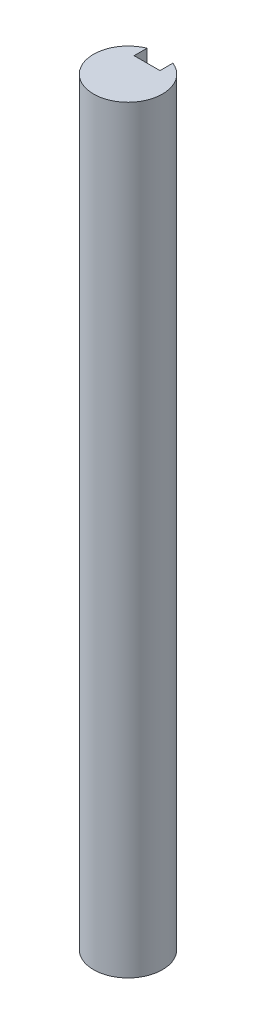
SolidWorks part; units mm, degrees
material "1023 Carbon Steel Sheet (SS)"
ref_plane "Front Plane" through (0, 0, 0) normal (0, 0, 1) x (1, 0, 0)
ref_plane "Top Plane" through (0, 0, 0) normal (0, 1, 0) x (1, 0, 0)
ref_plane "Right Plane" through (0, 0, 0) normal (1, 0, 0) x (0, 0, -1)
sketch "Sketch1" plane through (0, 0, 0) normal (0, 1, 0) x (1, 0, 0)
  line L0 (-1.1906, 2.9433) -> (-1.1906, 1.7527)
  line L1 (-1.1906, 1.7527) -> (1.1906, 1.7527)
  line L2 (1.1906, 1.7527) -> (1.1906, 2.9433)
  arc A0 (-1.1906, 2.9433) -> (1.1906, 2.9433) centre (0, 0) ccw
  point P5 (0, 1.7527)
  dimension "D1" = 6.35
  dimension "D2" = 2.3813
  dimension "D3" = 1.1906
extrude "Boss-Extrude1" add sketch "Sketch1" along normal blind 69.85
